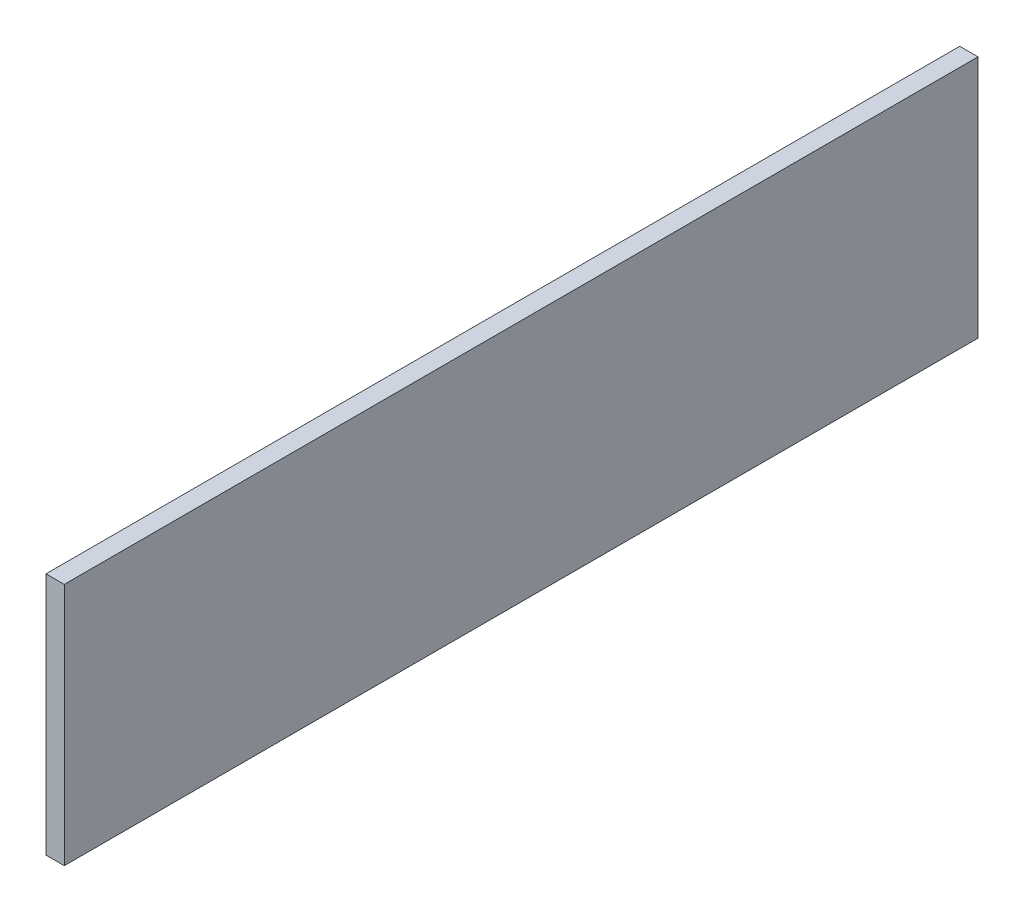
SolidWorks part; units mm, degrees
material "Ceramic Porcelain"
ref_plane "Front Plane" through (0, 0, 0) normal (0, 0, 1) x (1, 0, 0)
ref_plane "Top Plane" through (0, 0, 0) normal (0, 1, 0) x (1, 0, 0)
ref_plane "Right Plane" through (0, 0, 0) normal (1, 0, 0) x (0, 0, -1)
sketch "Sketch1" plane through (0, 0, 0) normal (1, 0, 0) x (0, 0, -1)
  line L1 (-851.8519, 418.0556) -> (648.1481, 418.0556)
  line L2 (-851.8519, 418.0556) -> (-851.8519, 18.0556)
  line L3 (-851.8519, 18.0556) -> (648.1481, 18.0556)
  line L4 (648.1481, 418.0556) -> (648.1481, 18.0556)
  dimension "D1" = 1500
  dimension "D2" = 400
extrude "Boss-Extrude1" add sketch "Sketch1" along normal blind 30
